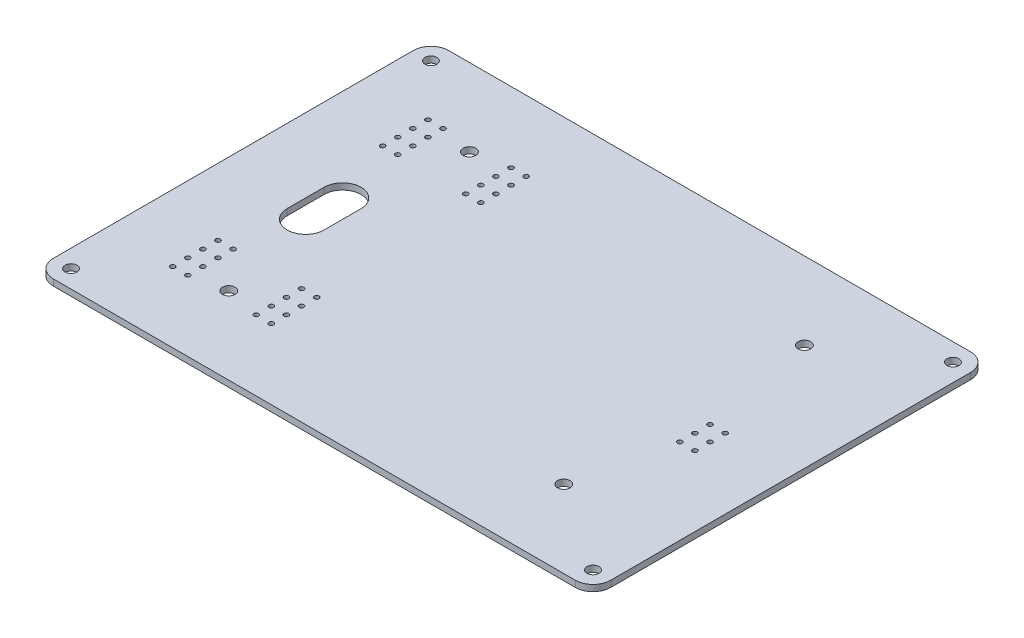
SolidWorks part; units mm, degrees
material "A-Glass Fiber"
ref_plane "Front Plane" through (0, 0, 0) normal (0, 0, 1) x (1, 0, 0)
ref_plane "Top Plane" through (0, 0, 0) normal (0, 1, 0) x (1, 0, 0)
ref_plane "Right Plane" through (0, 0, 0) normal (1, 0, 0) x (0, 0, -1)
sketch "Sketch1" plane through (0, 0, 0) normal (0, 1, 0) x (1, 0, 0)
  line L0 (0, 0) -> (70.7165, 0) construction
  line L1 (-65.4106, -49.8688) -> (66.2376, -49.8688)
  line L2 (-69.8896, -45.3898) -> (-69.8896, 45.3898)
  line L3 (-65.4106, 49.8688) -> (66.2376, 49.8688)
  line L4 (70.7165, -45.3898) -> (70.7165, 45.3898)
  line L5 (-69.8896, -49.8688) -> (70.7165, 49.8688) construction
  line L6 (-69.8896, 49.8688) -> (70.7165, -49.8688) construction
  line L10 (-71.1596, 54.5719) -> (-71.1596, 45.5295) construction
  arc A0 (-69.8896, 45.3898) -> (-65.4106, 49.8688) centre (-65.4106, 45.3898) cw
  arc A1 (66.2376, 49.8688) -> (70.7165, 45.3898) centre (66.2376, 45.3898) cw
  arc A2 (70.7165, -45.3898) -> (66.2376, -49.8688) centre (66.2376, -45.3898) cw
  arc A3 (-65.4106, -49.8688) -> (-69.8896, -45.3898) centre (-65.4106, -45.3898) cw
  point P0 (0.4135, 0)
  dimension "D1" = 1.27
extrude "Boss-Extrude1" add sketch "Sketch1" against normal blind 1.5875
sketch "Sketch2" plane through (0, 0, 0) normal (0, 1, 0) x (1, 0, 0)
  circle A35 centre (-40.6725, -30.35) radius 1.5875
  circle A36 centre (-40.6725, -30.35) radius 1.5875
  circle A37 centre (-40.6725, 30.35) radius 1.5875
  circle A38 centre (-40.6725, 30.35) radius 1.5875
  circle A39 centre (43.8275, 30.35) radius 1.5875
  circle A40 centre (43.8275, 30.35) radius 1.5875
  circle A41 centre (43.8275, -30.35) radius 1.5875
  circle A42 centre (43.8275, -30.35) radius 1.5875
  dimension "D27" = 0
  dimension "D28" = 0
  dimension "D29" = 0
  dimension "D30" = 0
extrude "Cut-Extrude1" cut sketch "Sketch2" against normal through all
sketch "Sketch3" plane through (0, 0, 0) normal (0, 1, 0) x (1, 0, 0)
  line L5 (-46.6035, 4.285) -> (-46.6035, -5.035) construction
  line L6 (-41.9335, 4.285) -> (-41.9335, -5.035)
  line L7 (-51.2735, 4.285) -> (-51.2735, -5.035)
  line L17 (-43.2035, 3.375) -> (-41.9335, 3.375) construction
  line L18 (-44.8535, 7.2) -> (-44.1998, 8.2889) construction
  line L19 (-46.6035, 7.2) -> (-46.6035, 8.955) construction
  line L20 (-44.8535, 7.2) -> (-48.3535, 7.2) construction
  line L21 (-46.6035, -7.95) -> (-46.6035, -9.705) construction
  line L22 (-48.3535, -7.95) -> (-44.8535, -7.95) construction
  arc A13 (-41.9335, 4.285) -> (-51.2735, 4.285) centre (-46.6035, 4.285) ccw
  arc A14 (-51.2735, -5.035) -> (-41.9335, -5.035) centre (-46.6035, -5.035) ccw
  arc A17 (-44.8535, 0.46) -> (-44.8535, 6.29) centre (-46.6035, 3.375) ccw construction
  point P2 (-46.6035, -0.375)
  dimension "D1" = 1.27
extrude "Cut-Extrude2" cut sketch "Sketch3" against normal through all
sketch "Sketch4" plane through (0, -1.5875, 0) normal (0, -1, 0) x (1, 0, 0)
  line L4 (-34.35, -10.348) -> (-39.27, -10.348)
  line L5 (-34.35, -25.08) -> (-34.35, -10.348)
  line L6 (-39.27, -25.08) -> (-34.35, -25.08)
  line L7 (-39.27, -10.348) -> (-39.27, -25.08)
  line L8 (-34.35, -10.348) -> (-39.27, -10.348)
  line L9 (-34.35, -25.08) -> (-34.35, -10.348)
  line L10 (-39.27, -25.08) -> (-34.35, -25.08)
  line L11 (-39.27, -10.348) -> (-39.27, -25.08)
  line L12 (-34.35, 25.63) -> (-39.27, 25.63)
  line L13 (-34.35, 10.898) -> (-34.35, 25.63)
  line L14 (-39.27, 10.898) -> (-34.35, 10.898)
  line L15 (-39.27, 25.63) -> (-39.27, 10.898)
  line L16 (-34.35, 25.63) -> (-39.27, 25.63)
  line L17 (-34.35, 10.898) -> (-34.35, 25.63)
  line L18 (-39.27, 10.898) -> (-34.35, 10.898)
  line L19 (-39.27, 25.63) -> (-39.27, 10.898)
  line L20 (-44.42, 10.898) -> (-39.5, 10.898)
  line L21 (-39.5, 10.898) -> (-39.5, 25.63)
  line L22 (-39.5, 25.63) -> (-44.42, 25.63)
  line L23 (-44.42, 25.63) -> (-44.42, 10.898)
  line L24 (-44.42, 10.898) -> (-39.5, 10.898)
  line L25 (-39.5, 10.898) -> (-39.5, 25.63)
  line L26 (-39.5, 25.63) -> (-44.42, 25.63)
  line L27 (-44.42, 25.63) -> (-44.42, 10.898)
  line L28 (-39.5, -10.348) -> (-44.42, -10.348)
  line L29 (-39.5, -25.08) -> (-39.5, -10.348)
  line L30 (-44.42, -25.08) -> (-39.5, -25.08)
  line L31 (-44.42, -10.348) -> (-44.42, -25.08)
  line L32 (-39.5, -10.348) -> (-44.42, -10.348)
  line L33 (-39.5, -25.08) -> (-39.5, -10.348)
  line L34 (-44.42, -25.08) -> (-39.5, -25.08)
  line L35 (-44.42, -10.348) -> (-44.42, -25.08)
  line L36 (35.46, 13.148) -> (40.38, 13.148)
  line L37 (35.46, 27.88) -> (35.46, 13.148)
  line L38 (40.38, 27.88) -> (35.46, 27.88)
  line L39 (40.38, 13.148) -> (40.38, 27.88)
  line L40 (35.46, 13.148) -> (40.38, 13.148)
  line L41 (35.46, 27.88) -> (35.46, 13.148)
  line L42 (40.38, 27.88) -> (35.46, 27.88)
  line L43 (40.38, 13.148) -> (40.38, 27.88)
  dimension "D1" = 0
  dimension "D2" = 0
  dimension "D3" = 0
  dimension "D4" = 0
  dimension "D5" = 0
sketch "Sketch6" plane through (0, -1.5875, 0) normal (0, -1, 0) x (1, 0, 0)
  line L0 (-20.19, 27.65) -> (-20.19, 33.65) construction
  line L1 (-20.19, 33.65) -> (-14.19, 33.65) construction
  line L2 (-14.19, 33.65) -> (-14.19, 27.65) construction
  line L3 (-14.19, 27.65) -> (-20.19, 27.65) construction
  line L4 (33.69, -6.45) -> (33.69, -22.45)
  line L5 (54.59, -6.45) -> (33.69, -6.45)
  line L6 (54.59, -22.45) -> (54.59, -6.45)
  line L7 (33.69, -22.45) -> (54.59, -22.45)
  line L8 (33.69, -6.45) -> (33.69, -22.45)
  line L9 (54.59, -6.45) -> (33.69, -6.45)
  line L10 (54.59, -22.45) -> (54.59, -6.45)
  line L11 (33.69, -22.45) -> (54.59, -22.45)
  line L20 (-8.69, 27.65) -> (-8.69, 33.65) construction
  line L21 (-8.69, 33.65) -> (-2.69, 33.65) construction
  line L22 (-2.69, 33.65) -> (-2.69, 27.65) construction
  line L23 (-2.69, 27.65) -> (-8.69, 27.65) construction
  line L24 (-20.19, 27.65) -> (-20.19, 33.65)
  line L25 (-20.19, 33.65) -> (-14.19, 33.65)
  line L26 (-14.19, 33.65) -> (-14.19, 27.65)
  line L27 (-14.19, 27.65) -> (-20.19, 27.65)
  line L28 (-8.69, 27.65) -> (-8.69, 33.65)
  line L29 (-8.69, 33.65) -> (-2.69, 33.65)
  line L30 (-2.69, 33.65) -> (-2.69, 27.65)
  line L31 (-2.69, 27.65) -> (-8.69, 27.65)
  line L80 (55.31, -35.15) -> (55.31, 35.15)
  line L82 (55.31, 35.15) -> (-55.31, 35.15)
  line L84 (-55.31, 35.15) -> (-55.31, -35.15)
  line L86 (-55.31, -35.15) -> (55.31, -35.15)
  line L92 (55.31, -35.15) -> (55.31, 35.15)
  line L94 (55.31, 35.15) -> (-55.31, 35.15)
  line L96 (-55.31, 35.15) -> (-55.31, -35.15)
  line L98 (-55.31, -35.15) -> (55.31, -35.15)
  circle A0 centre (-17.19, 30.65) radius 1.75 construction
  circle A1 centre (-5.69, 30.65) radius 1.75 construction
  circle A2 centre (-17.19, 30.65) radius 1.75
  circle A3 centre (-5.69, 30.65) radius 1.75
  dimension "D1" = 0
  dimension "D2" = 0
sketch "Sketch7" plane through (0, -1.5875, 0) normal (0, -1, 0) x (1, 0, 0)
  circle A1 centre (49.2175, 6.483) radius 0.6
  circle A2 centre (49.2175, 6.483) radius 0.6
  circle A3 centre (-49.1085, -32.125) radius 0.6
  circle A4 centre (-49.1085, -32.125) radius 0.6
  circle A5 centre (-28.1535, -32.125) radius 0.6
  circle A6 centre (-28.1535, -32.125) radius 0.6
  circle A7 centre (-28.1535, 20.707) radius 0.6
  circle A8 centre (-28.1535, 20.707) radius 0.6
  circle A9 centre (-49.2355, 20.707) radius 0.6
  circle A10 centre (-49.2355, 20.707) radius 0.6
  circle A11 centre (-31.9635, 20.707) radius 0.6
  circle A12 centre (-31.9635, 20.707) radius 0.6
  circle A13 centre (-53.0455, 20.707) radius 0.6
  circle A14 centre (-53.0455, 20.707) radius 0.6
  circle A15 centre (-31.9635, 28.327) radius 0.6
  circle A16 centre (-31.9635, 28.327) radius 0.6
  circle A17 centre (-53.0455, 28.327) radius 0.6
  circle A18 centre (-53.0455, 28.327) radius 0.6
  circle A19 centre (-31.9635, 24.517) radius 0.6
  circle A20 centre (-31.9635, 24.517) radius 0.6
  circle A21 centre (-53.0455, 24.517) radius 0.6
  circle A22 centre (-53.0455, 24.517) radius 0.6
  circle A23 centre (-31.9635, -28.315) radius 0.6
  circle A24 centre (-31.9635, -28.315) radius 0.6
  circle A25 centre (-52.9185, -28.315) radius 0.6
  circle A26 centre (-52.9185, -28.315) radius 0.6
  circle A27 centre (-31.9635, -32.125) radius 0.6
  circle A28 centre (-31.9635, -32.125) radius 0.6
  circle A29 centre (-52.9185, -32.125) radius 0.6
  circle A30 centre (-52.9185, -32.125) radius 0.6
  circle A31 centre (-28.1535, 24.517) radius 0.6
  circle A32 centre (-28.1535, 24.517) radius 0.6
  circle A33 centre (-49.2355, 24.517) radius 0.6
  circle A34 centre (-49.2355, 24.517) radius 0.6
  circle A35 centre (-31.9635, 32.137) radius 0.6
  circle A36 centre (-31.9635, 32.137) radius 0.6
  circle A37 centre (-53.0455, 32.137) radius 0.6
  circle A38 centre (-53.0455, 32.137) radius 0.6
  circle A39 centre (-31.9635, -20.695) radius 0.6
  circle A40 centre (-31.9635, -20.695) radius 0.6
  circle A41 centre (-52.9185, -20.695) radius 0.6
  circle A42 centre (-52.9185, -20.695) radius 0.6
  circle A43 centre (-31.9635, -24.505) radius 0.6
  circle A44 centre (-31.9635, -24.505) radius 0.6
  circle A45 centre (-52.9185, -24.505) radius 0.6
  circle A46 centre (-52.9185, -24.505) radius 0.6
  circle A47 centre (-28.1535, 32.137) radius 0.6
  circle A48 centre (-28.1535, 32.137) radius 0.6
  circle A49 centre (-49.2355, 32.137) radius 0.6
  circle A50 centre (-49.2355, 32.137) radius 0.6
  circle A51 centre (-28.1535, 28.327) radius 0.6
  circle A52 centre (-28.1535, 28.327) radius 0.6
  circle A53 centre (-49.2355, 28.327) radius 0.6
  circle A54 centre (-49.2355, 28.327) radius 0.6
  circle A55 centre (-28.1535, -24.505) radius 0.6
  circle A56 centre (-28.1535, -24.505) radius 0.6
  circle A57 centre (-49.1085, -24.505) radius 0.6
  circle A58 centre (-49.1085, -24.505) radius 0.6
  circle A59 centre (-28.1535, -28.315) radius 0.6
  circle A60 centre (-28.1535, -28.315) radius 0.6
  circle A61 centre (-49.1085, -28.315) radius 0.6
  circle A62 centre (-49.1085, -28.315) radius 0.6
  circle A63 centre (49.2175, 2.673) radius 0.6
  circle A64 centre (49.2175, 2.673) radius 0.6
  circle A65 centre (53.0275, -1.137) radius 0.6
  circle A66 centre (53.0275, -1.137) radius 0.6
  circle A67 centre (53.0275, 2.673) radius 0.6
  circle A68 centre (53.0275, 2.673) radius 0.6
  circle A69 centre (53.0275, 6.483) radius 0.6
  circle A70 centre (53.0275, 6.483) radius 0.6
  circle A71 centre (-28.1535, -20.695) radius 0.6
  circle A72 centre (-28.1535, -20.695) radius 0.6
  circle A73 centre (-49.1085, -20.695) radius 0.6
  circle A74 centre (-49.1085, -20.695) radius 0.6
  circle A75 centre (49.2175, -1.137) radius 0.6
  circle A76 centre (49.2175, -1.137) radius 0.6
  dimension "D1" = 0
  dimension "D2" = 0
  dimension "D3" = 0
  dimension "D4" = 0
  dimension "D5" = 0
  dimension "D6" = 0
  dimension "D7" = 0
  dimension "D8" = 0
  dimension "D9" = 0
  dimension "D10" = 0
  dimension "D11" = 0
  dimension "D12" = 0
  dimension "D13" = 0
  dimension "D14" = 0
  dimension "D15" = 0
  dimension "D16" = 0
  dimension "D17" = 0
  dimension "D18" = 0
  dimension "D19" = 0
  dimension "D20" = 0
  dimension "D21" = 0
  dimension "D22" = 0
  dimension "D23" = 0
  dimension "D24" = 0
  dimension "D25" = 0
  dimension "D26" = 0
  dimension "D27" = 0
  dimension "D28" = 0
  dimension "D29" = 0
  dimension "D30" = 0
  dimension "D31" = 0
  dimension "D32" = 0
  dimension "D33" = 0
  dimension "D34" = 0
  dimension "D35" = 0
  dimension "D36" = 0
  dimension "D37" = 0
  dimension "D38" = 0
extrude "Cut-Extrude3" cut sketch "Sketch7" against normal through all
sketch "Sketch8" plane through (0, -1.5875, 0) normal (0, -1, 0) x (1, 0, 0)
  line L4 (-47.9085, -18.395) -> (-54.7585, -18.395)
  line L5 (-47.9085, -34.425) -> (-47.9085, -18.395)
  line L6 (-54.7585, -34.425) -> (-47.9085, -34.425)
  line L7 (-54.7585, -18.395) -> (-54.7585, -34.425)
  line L8 (-47.9085, -18.395) -> (-54.7585, -18.395)
  line L9 (-47.9085, -34.425) -> (-47.9085, -18.395)
  line L10 (-54.7585, -34.425) -> (-47.9085, -34.425)
  line L11 (-54.7585, -18.395) -> (-54.7585, -34.425)
  line L12 (-54.8855, 18.407) -> (-48.0355, 18.407)
  line L13 (-48.0355, 18.407) -> (-48.0355, 34.437)
  line L14 (-48.0355, 34.437) -> (-54.8855, 34.437)
  line L15 (-54.8855, 34.437) -> (-54.8855, 18.407)
  line L16 (-54.8855, 18.407) -> (-48.0355, 18.407)
  line L17 (-48.0355, 18.407) -> (-48.0355, 34.437)
  line L18 (-48.0355, 34.437) -> (-54.8855, 34.437)
  line L19 (-54.8855, 34.437) -> (-54.8855, 18.407)
  line L20 (-33.8035, -18.395) -> (-33.8035, -34.425)
  line L21 (-33.8035, -34.425) -> (-26.9535, -34.425)
  line L22 (-26.9535, -34.425) -> (-26.9535, -18.395)
  line L23 (-26.9535, -18.395) -> (-33.8035, -18.395)
  line L24 (-33.8035, -18.395) -> (-33.8035, -34.425)
  line L25 (-33.8035, -34.425) -> (-26.9535, -34.425)
  line L26 (-26.9535, -34.425) -> (-26.9535, -18.395)
  line L27 (-26.9535, -18.395) -> (-33.8035, -18.395)
  line L28 (-26.9535, 34.437) -> (-33.8035, 34.437)
  line L29 (-26.9535, 18.407) -> (-26.9535, 34.437)
  line L30 (-33.8035, 18.407) -> (-26.9535, 18.407)
  line L31 (-33.8035, 34.437) -> (-33.8035, 18.407)
  line L32 (-26.9535, 34.437) -> (-33.8035, 34.437)
  line L33 (-26.9535, 18.407) -> (-26.9535, 34.437)
  line L34 (-33.8035, 18.407) -> (-26.9535, 18.407)
  line L35 (-33.8035, 34.437) -> (-33.8035, 18.407)
  line L36 (47.8175, 8.783) -> (47.8175, -3.437)
  line L37 (47.8175, -3.437) -> (54.6675, -3.437)
  line L38 (54.6675, -3.437) -> (54.6675, 8.783)
  line L39 (54.6675, 8.783) -> (47.8175, 8.783)
  line L40 (47.8175, 8.783) -> (47.8175, -3.437)
  line L41 (47.8175, -3.437) -> (54.6675, -3.437)
  line L42 (54.6675, -3.437) -> (54.6675, 8.783)
  line L43 (54.6675, 8.783) -> (47.8175, 8.783)
  dimension "D1" = 0
  dimension "D2" = 0
  dimension "D3" = 0
  dimension "D4" = 0
  dimension "D5" = 0
sketch "Sketch9" plane through (0, 0, 0) normal (0, 1, 0) x (1, 0, 0)
  circle A0 centre (-65.4106, 45.3898) radius 1.5
  circle A1 centre (-65.4106, -45.3898) radius 1.5
  circle A2 centre (66.2376, 45.3898) radius 1.5
  circle A3 centre (66.2376, -45.3898) radius 1.5
  dimension "D1" = 3
extrude "Cut-Extrude4" cut sketch "Sketch9" against normal through all
sketch "Sketch11" plane through (0, -1.5875, 0) normal (0, -1, 0) x (1, 0, 0)
  line L0 (-56.1414, -50.8932) -> (-56.1414, -38.1932) construction
  line L1 (-56.1414, -50.8932) -> (-56.1414, -38.1932)
sketch "Sketch12" plane through (0, -1.5875, 0) normal (0, -1, 0) x (1, 0, 0)
  circle A0 centre (-40.6725, -30.35) radius 3.81
  circle A1 centre (-40.6725, -30.35) radius 1.5875 construction
  circle A2 centre (-40.6725, 30.35) radius 3.81
  circle A3 centre (43.8275, 30.35) radius 3.81
  circle A4 centre (43.8275, -30.35) radius 3.81
  dimension "D1" = 7.62
equation "\"62.5mi\"=0.1"
